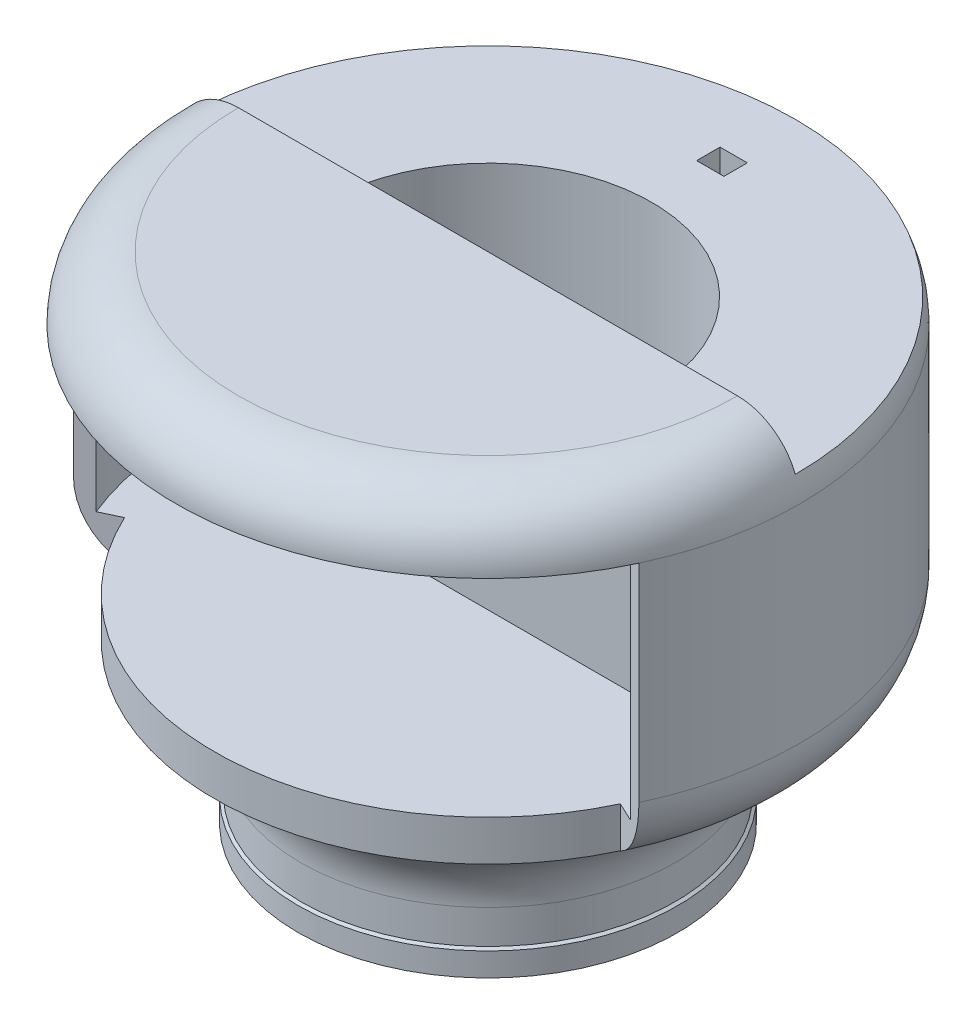
SolidWorks part; units mm, degrees
ref_plane "Front Plane" through (0, 0, 0) normal (0, 0, 1) x (1, 0, 0)
ref_plane "Top Plane" through (0, 0, 0) normal (0, 1, 0) x (1, 0, 0)
ref_plane "Right Plane" through (0, 0, 0) normal (1, 0, 0) x (0, 0, -1)
sketch "Sketch1" plane through (0, 0, 0) normal (0, 0, 1) x (1, 0, 0)
  line L0 (0, 0) -> (0, 90.2242) construction
  line L28 (0, 63.4279) -> (32, 63.4279)
  line L29 (40, 55.4279) -> (40, 28.8468)
  line L30 (22.5, 0) -> (24.35, 0)
  line L31 (24.35, 0) -> (24.35, 3)
  line L32 (24.35, 3) -> (24, 3.25)
  line L33 (24, 3.25) -> (24, 7.5811)
  line L34 (28.5399, 15.9588) -> (35.4601, 20.4691)
  line L35 (0, 13) -> (22, 13)
  line L36 (22.5, 12.5) -> (22.5, 0)
  line L37 (0, 13) -> (0, 63.4279)
  arc A0 (22, 13) -> (22.5, 12.5) centre (22, 12.5) cw
  arc A1 (24, 7.5811) -> (28.5399, 15.9588) centre (34, 7.5811) cw
  arc A2 (35.4601, 20.4691) -> (40, 28.8468) centre (30, 28.8468) ccw
  arc A3 (32, 63.4279) -> (40, 55.4279) centre (32, 55.4279) cw
  point P11 (22.9, 63.4279)
  point P18 (22.5, 13)
  point P21 (24, 13)
  point P24 (40, 23.4279)
  point P27 (40, 63.4279)
  point P28 (28.5604, 23.4279)
  point P31 (22.5, 17)
  dimension "D8" = 9.75
  dimension "D9" = 0.5
  dimension "D4" = 1.85
  dimension "D1" = 22.5
  dimension "D10" = 10
  dimension "D11" = 10
  dimension "D12" = 8
  dimension "D2" = 40
  dimension "D3" = 40
  dimension "D5" = 1.5
  dimension "D6" = 3
  dimension "D7" = 13
revolve "Revolve1" add sketch "Sketch1" angle 360 about L0
ref_plane "Plane1" through (0, 13, 0) normal (0, -1, 0) x (-1, 0, 0)
sketch "Sketch18" plane through (0, 0, 0) normal (0, 0, 1) x (1, 0, 0)
  line L0 (0, 0) -> (0, 101.5813) construction
  line L1 (-24.35, 0) -> (24.35, 0) construction
sketch "Sketch3" plane through (0, 0, 0) normal (0, 0, 1) x (1, 0, 0)
  point P0 (1.2404, 19.1989)
ref_point "Point1"
ref_plane "Plane2" through (0, 0, 22.9) normal (0, 0, 1) x (1, 0, 0)
ref_plane "Plane3" through (0, 0, 40) normal (0, 0, 1) x (1, 0, 0)
ref_plane "Plane4" through (0, 55.4279, 0) normal (0, 1, 0) x (1, 0, 0)
sketch "Sketch9" plane through (0, 55.4279, 0) normal (0, 1, 0) x (1, 0, 0)
  line L1 (-24, -1.7631) -> (24, -1.7631)
  arc A2 (-37, -1.6015) -> (37, -2.3985) centre (0, -2) ccw
  arc A3 (-37, -1.6015) -> (37, -2.3985) centre (0, -2) cw
  arc A6 (-24, -1.7631) -> (24, -1.7631) centre (0, -0.0603) cw
  dimension "D1" = 74
  dimension "D3" = 13
  dimension "D4" = 13
ref_plane "Plane5" through (0, 13, 0) normal (0, -1, 0) x (-1, 0, 0)
sketch "Sketch11" plane through (0, 13, 0) normal (0, -1, 0) x (-1, 0, 0)
  line L0 (-21, 0) -> (21, 0)
  arc A1 (-21, 0) -> (21, 0) centre (0, 0) cw
  dimension "D1" = 42
extrude "Cut-Extrude3" cut sketch "Sketch11" against normal blind 60
ref_plane "Plane6" through (0, 0, -40) normal (0, 0, -1) x (-1, 0, 0)
extrude "Cut-Extrude5" cut sketch "Sketch9" against normal blind 30 and the other way blind 2
sketch "Sketch19" plane through (0, 0, 0) normal (1, 0, 0) x (0, 0, -1)
  line L0 (-47.0647, 55.4279) -> (-35.0647, 55.4279)
  line L1 (31.2976, 55.4279) -> (-31.2976, 55.4279) construction
  line L2 (-35.0647, 55.4279) -> (-35.0647, 18.9279)
  line L3 (-35.0647, 18.9279) -> (-47.0647, 18.9279)
  line L4 (-47.0647, 18.9279) -> (-47.0647, 55.4279)
  dimension "D1" = 12
  dimension "D2" = 36.5
revolve "Cut-Revolve2" cut sketch "Sketch19" angle 65 about L0 other way angle 65
ref_plane "Plane7" through (0, 0, 22.5) normal (0, 0, -1) x (-1, 0, 0)
sketch "Sketch21" plane through (0, 0, 22.5) normal (0, 0, -1) x (-1, 0, 0)
  line L0 (0, 0) -> (0, 101.5813) construction
  line L1 (-1.625, 4) -> (1.625, 4)
  line L2 (-1.625, 4) -> (-1.625, 0)
  line L3 (-1.625, 0) -> (1.625, 0)
  line L4 (1.625, 4) -> (1.625, 0)
  line L5 (-1.625, 4) -> (1.625, 0) construction
  line L6 (-1.625, 0) -> (1.625, 4) construction
  line L7 (-22.5, 0) -> (22.5, 0) construction
  point P0 (0, 2)
  dimension "D1" = 4
  dimension "D2" = 3.25
extrude "Boss-Extrude3" add sketch "Sketch21" along normal blind 1.35
pattern_circular "CirPattern1" count 5 over 360 about axis through (0, 0, 0) along (0, -1, 0) of "Boss-Extrude3"
ref_plane "Plane8" through (0, 20.4691, 0) normal (0, 1, 0) x (1, 0, 0)
sketch "Sketch22" plane through (0, 63.4279, 0) normal (0, 1, 0) x (1, 0, 0)
  line L0 (-40, 0) -> (40, 0)
  arc A0 (-40, 0) -> (40, 0) centre (0, 0) cw
  arc A1 (36.2523, -16.9047) -> (-36.2523, -16.9047) centre (0, 0) ccw construction
extrude "Cut-Extrude9" cut sketch "Sketch22" against normal blind 5
sketch "Sketch23" plane through (0, 0, -40) normal (0, 0, -1) x (-1, 0, 0)
  line L0 (0, 0) -> (0, 101.5813) construction
  line L1 (44, 55.4279) -> (-44, 55.4279) construction
  circle A0 centre (0, 42.1379) radius 10
  dimension "D1" = 20
  dimension "D2" = 13.29
extrude "Cut-Extrude10" cut sketch "Sketch23" against normal blind 10
fillet "Fillet1" radius 5 1 edges at (1.8994, 32.3199, -34.9534)
sketch "Sketch24" plane through (0, 58.4279, 0) normal (0, 1, 0) x (1, 0, 0)
  line L1 (-6, 32.5) -> (6, 32.5)
  line L2 (-6, 32.5) -> (-6, 27.5)
  line L3 (-6, 27.5) -> (6, 27.5)
  line L4 (6, 32.5) -> (6, 27.5)
  line L5 (-6, 32.5) -> (6, 27.5) construction
  line L6 (-6, 27.5) -> (6, 32.5) construction
  arc A0 (39.4162, 0) -> (-39.4162, 0) centre (0, 0) ccw construction
  point P0 (0, 30)
  dimension "D1" = 30
  dimension "D2" = 5
  dimension "D3" = 12
extrude "Boss-Extrude4" add sketch "Sketch24" against normal blind 8
sketch "Sketch26" plane through (0, 58.4279, 0) normal (0, 1, 0) x (1, 0, 0)
  line L1 (-1.75, 31.5) -> (1.75, 31.5)
  line L2 (-1.75, 31.5) -> (-1.75, 28.5)
  line L3 (-1.75, 28.5) -> (1.75, 28.5)
  line L4 (1.75, 31.5) -> (1.75, 28.5)
  line L5 (-1.75, 31.5) -> (1.75, 28.5) construction
  line L6 (-1.75, 28.5) -> (1.75, 31.5) construction
  arc A0 (39.4162, 0) -> (-39.4162, 0) centre (0, 0) ccw construction
  point P0 (0, 30)
  dimension "D1" = 30
  dimension "D2" = 3
  dimension "D3" = 3.5
extrude "Cut-Extrude11" cut sketch "Sketch26" against normal blind 10
sketch "Sketch27" plane through (6, 0, 0) normal (1, 0, 0) x (0, 0, -1)
  line L0 (32.5, 50.4279) -> (32.5, 57.4279) construction
  line L1 (28.0394, 56.918) -> (31.9606, 56.918)
  line L2 (28.0394, 56.918) -> (28.0394, 50.9378)
  line L3 (28.0394, 50.9378) -> (31.9606, 50.9378)
  line L4 (31.9606, 56.918) -> (31.9606, 50.9378)
  line L5 (28.0394, 56.918) -> (31.9606, 50.9378) construction
  line L6 (28.0394, 50.9378) -> (31.9606, 56.918) construction
  line L7 (27.5, 50.4279) -> (27.5, 57.4279) construction
  line L8 (27.5, 50.4279) -> (32.5, 50.4279) construction
  point P0 (30, 53.9279)
  dimension "D1" = 5
  dimension "D2" = 3.5
extrude "Cut-Extrude12" cut sketch "Sketch27" against normal blind 5
ref_plane "Plane9" through (-39.4162, 58.4279, 0) normal (0.375, 0.927, 0) x (0.927, -0.375, 0)
